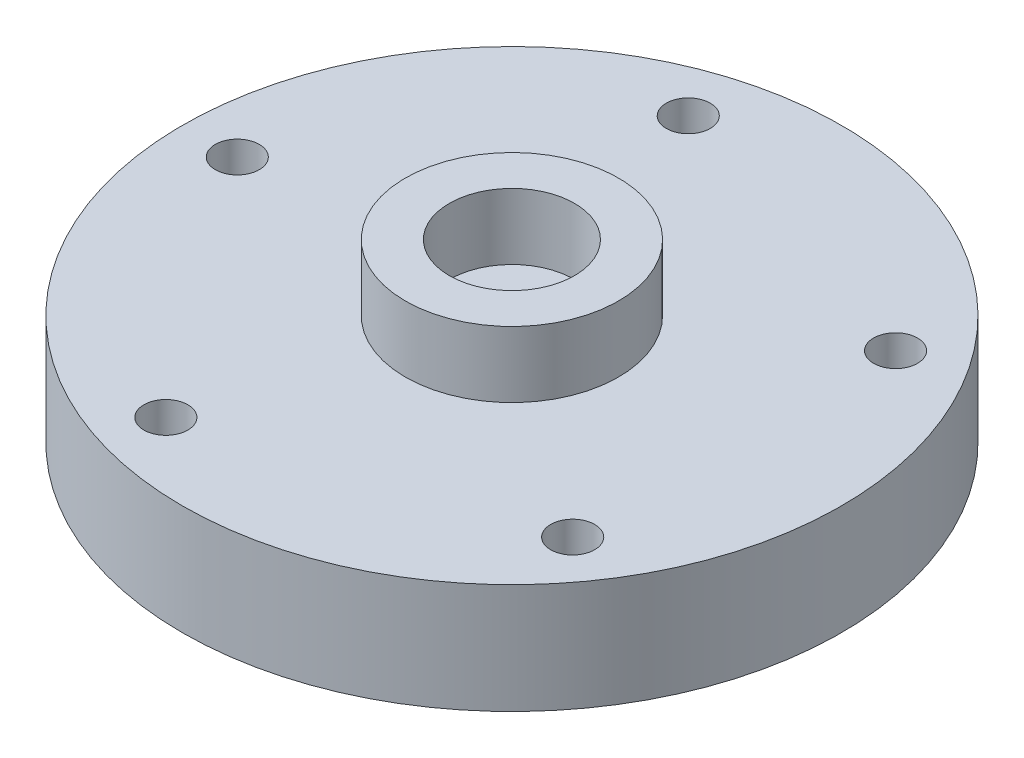
SolidWorks part; units mm, degrees
ref_plane "Front Plane" through (0, 0, 0) normal (0, 0, 1) x (1, 0, 0)
ref_plane "Top Plane" through (0, 0, 0) normal (0, 1, 0) x (1, 0, 0)
ref_plane "Right Plane" through (0, 0, 0) normal (1, 0, 0) x (0, 0, -1)
sketch "Sketch1" plane through (0, 0, 0) normal (0, 1, 0) x (1, 0, 0)
  line L0 (-12.5, 0) -> (12.5, 0) construction
  circle A0 centre (0, 0) radius 15
  circle A1 centre (0, 0) radius 12.5
  circle A2 centre (0, 0) radius 1
  circle A3 centre (-12.5, 0) radius 1
  circle A4 centre (-3.8627, 11.8882) radius 1
  circle A5 centre (10.1127, 7.3473) radius 1
  circle A6 centre (10.1127, -7.3473) radius 1
  circle A7 centre (-3.8627, -11.8882) radius 1
  point P19 (0, 0)
  dimension "D1" = 30
  dimension "D2" = 2.5
  dimension "D3" = 2
  dimension "D4" = 2
  dimension "D5" = 5
extrude "Boss-Extrude1" add sketch "Sketch1" along normal blind 2 and the other way blind 3 contours A0 A7 A1 A3 A4 A5 A6 | L0 A3 A1 A7 A6 A2 | A3 L0 A2 A1 A5 A4 region at (0, 0, -5.3016) region at (0, 0, 5.3016) region at (-14.5757, 0, 0)
sketch "Sketch2" plane through (0, 2, 0) normal (0, 1, 0) x (1, 0, 0)
  circle A0 centre (0, 0) radius 2.85
  circle A1 centre (0, 0) radius 4.85
  dimension "D1" = 5.7
  dimension "D2" = 2
extrude "Boss-Extrude3" add sketch "Sketch2" along normal blind 3 contours A1 A0 region at (-4.7128, 2, 0)
sketch "Sketch4" plane through (0, 2, 0) normal (0, 1, 0) x (1, 0, 0)
  circle A0 centre (0, 0) radius 2
sketch "Sketch5" plane through (0, -3, 0) normal (0, -1, 0) x (1, 0, 0)
  circle A0 centre (0, 0) radius 2
extrude "Cut-Extrude2" cut sketch "Sketch5" against normal blind 1
